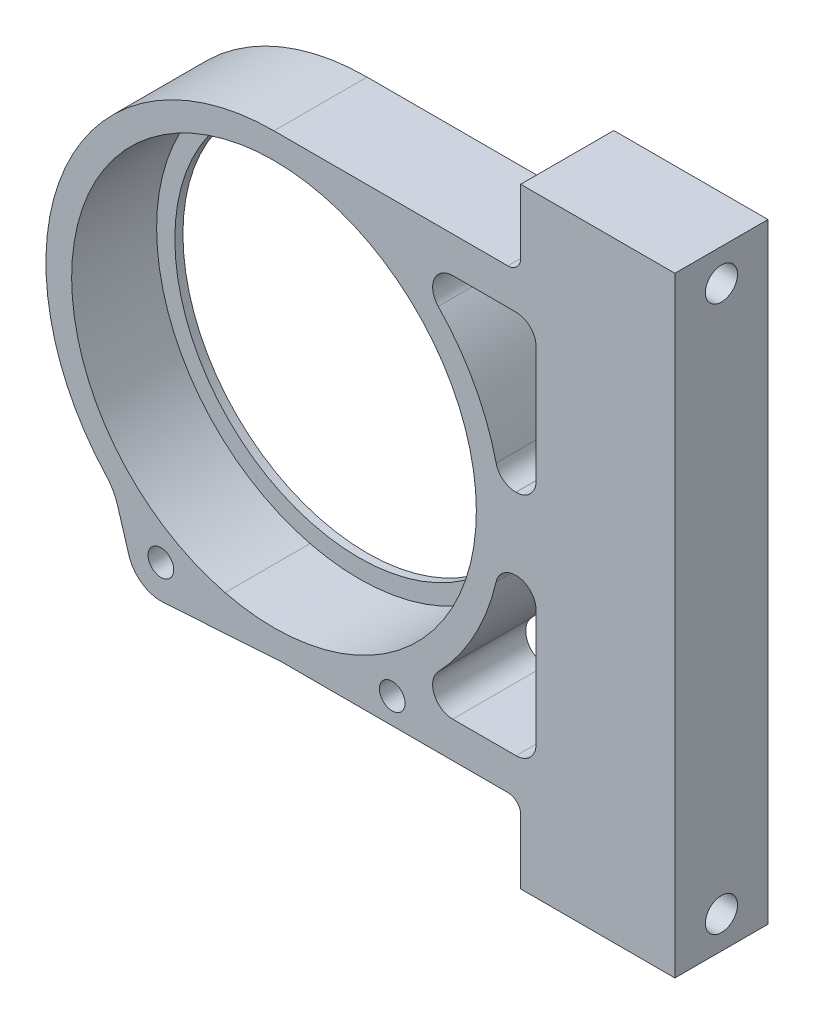
SolidWorks part; units mm, degrees
material "7075-T6 (SN)"
ref_plane "Front Plane" through (0, 0, 0) normal (0, 0, 1) x (1, 0, 0)
ref_plane "Top Plane" through (0, 0, 0) normal (0, 1, 0) x (1, 0, 0)
ref_plane "Right Plane" through (0, 0, 0) normal (1, 0, 0) x (0, 0, -1)
sketch "Sketch1" plane through (0, 0, 0) normal (0, 0, 1) x (1, 0, 0)
  line L0 (73.66, 75.4) -> (73.66, -75.4)
  line L1 (73.66, -1543.0888) -> (73.66, -1565.832) construction
  line L2 (73.66, 75.4) -> (60.96, 75.4)
  line L3 (60.96, 75.4) -> (60.96, 59.525)
  line L4 (57.785, 56.35) -> (0, 56.35)
  line L5 (73.66, -75.4) -> (60.96, -75.4)
  line L6 (60.96, -75.4) -> (60.96, -59.525)
  line L7 (57.785, -56.35) -> (0, -56.35)
  circle A0 centre (0, 0) radius 50
  arc A1 (0, 56.35) -> (0, -56.35) centre (0, 0) ccw
  circle A2 centre (0, 0) radius 56.35 construction
  arc A3 (60.96, -59.525) -> (57.785, -56.35) centre (57.785, -59.525) ccw
  arc A4 (60.96, 59.525) -> (57.785, 56.35) centre (57.785, 59.525) cw
  point P23 (60.96, 56.35)
  dimension "D1" = 50
  dimension "D5" = 3.175
  dimension "D2" = 6.35
  dimension "D3" = 12.7
  dimension "D4" = 19.05
extrude "Boss-Extrude1" add sketch "Sketch1" against normal blind 23
sketch "Sketch2" plane through (60.96, 0, 0) normal (-1, 0, 0) x (0, 0, 1)
  line L0 (-11.5, 75.4) -> (-11.5, -75.4) construction
  line L1 (-23, 75.4) -> (0, 75.4) construction
  line L2 (-23, -75.4) -> (0, -75.4) construction
  line L3 (-23, 67.4625) -> (0, 67.4625) construction
  line L4 (-23, 75.4) -> (-23, 59.525) construction
  line L5 (0, 75.4) -> (0, 59.525) construction
  line L6 (-23, -67.4625) -> (0, -67.4625) construction
  line L7 (-23, -59.525) -> (-23, -75.4) construction
  line L8 (0, -59.525) -> (0, -75.4) construction
  circle A0 centre (-11.5, 67.4625) radius 3.9687
  circle A1 centre (-11.5, -67.4625) radius 3.9687
  circle A2 centre (-11.5, 67.4625) radius 7.1374 construction
  dimension "D1" = 7.9375
  dimension "D2" = 14.2748
extrude "Cut-Extrude1" cut sketch "Sketch2" against normal blind 23
sketch "Sketch3" plane through (0, 0, -23) normal (0, 0, -1) x (-1, 0, 0)
  circle A0 centre (0, 0) radius 50 construction
  circle A1 centre (0, 0) radius 50
  circle A2 centre (0, 0) radius 45.5
  dimension "D1" = 45.5
extrude "Boss-Extrude2" add sketch "Sketch3" against normal blind 2
ref_plane "Plane1" through (0, 0, 0) normal (-0.9703, 0.2419, 0) x (0, 0, 1)
split line "Split Line1"
ref_plane "Plane2" through (73.66, 0, 0) normal (1, 0, 0) x (0, 0, -1)
ref_axis "Axis1" through (0, 0, -21) along (0, 0, 1)
ref_point "Point1"
sketch "Sketch4" plane through (0, 0, 0) normal (0, 0, 1) x (1, 0, 0)
  line L0 (64.77, 8.89) -> (64.77, 47.46)
  line L1 (64.77, -8.89) -> (64.77, 8.89) construction
  line L5 (57.785, 47.46) -> (0, 47.46)
  line L6 (64.77, 47.46) -> (30.3552, 47.46)
  line L7 (30.3552, -47.46) -> (64.77, -47.46)
  line L9 (0, -56.35) -> (57.785, -56.35) construction
  line L10 (64.77, -75.4) -> (64.77, 75.4)
  line L11 (64.77, -47.46) -> (64.77, -8.89)
  line L12 (56.3373, 0) -> (64.77, 0) construction
  line L13 (55.6315, -8.89) -> (64.77, -8.89)
  line L14 (55.6315, 8.89) -> (64.77, 8.89)
  line L15 (56.3373, 8.89) -> (64.77, 8.89) construction
  line L16 (56.3373, -8.89) -> (64.77, -8.89) construction
  arc A2 (30.3552, -47.46) -> (55.6315, -8.89) centre (0, 0) ccw
  arc A4 (55.6315, 8.89) -> (30.3552, 47.46) centre (0, 0) ccw
  arc A5 (55.6315, -8.89) -> (55.6315, 8.89) centre (0, 0) ccw construction
  dimension "D4" = 8.89
  dimension "D2" = 8.89
  dimension "D3" = 8.89
  dimension "D5" = 8.89
  dimension "D6" = 8.89
extrude "Cut-Extrude2" cut sketch "Sketch4" against normal through all
fillet "Fillet1" radius 4.953 8 edges at (64.77, -47.46, -11.5) (30.3552, -47.46, -11.5) (55.6315, -8.89, -11.5) (64.77, -8.89, -11.5) (64.77, 47.46, -11.5) (64.77, 8.89, -11.5) (55.6315, 8.89, -11.5) (30.3552, 47.46, -11.5)
sketch "Sketch5" plane through (73.66, 0, 0) normal (1, 0, 0) x (0, 0, -1)
  line L0 (11.5, 37.3) -> (11.5, -37.3) construction
  line L1 (15.945, 37.3) -> (15.945, -37.3)
  line L2 (7.055, 37.3) -> (7.055, -37.3)
  line L3 (11.5, -75.4) -> (11.5, -37.3) construction
  line L4 (23, -75.4) -> (0, -75.4) construction
  line L5 (11.5, 37.3) -> (11.5, 75.4) construction
  line L6 (23, 75.4) -> (0, 75.4) construction
  arc A0 (15.945, 37.3) -> (7.055, 37.3) centre (11.5, 37.3) ccw
  arc A1 (7.055, -37.3) -> (15.945, -37.3) centre (11.5, -37.3) ccw
  point P2 (11.5, 0)
  dimension "D1" = 8.89
  dimension "D2" = 38.1
extrude "Cut-Extrude3" [suppressed] cut sketch "Sketch5" against normal blind 16.51
sketch "Sketch6" plane through (0, 0, 0) normal (0, 0, 1) x (1, 0, 0)
  line L0 (-27.94, -50) -> (29.21, -50) construction
  line L1 (60.96, -75.4) -> (73.66, -75.4) construction
  line L2 (-76.2, -120.65) -> (-27.94, -50) construction
  line L3 (73.66, -75.4) -> (73.66, 75.4) construction
  line L4 (-22.8035, -35.7983) -> (-78.4053, -108.1429)
  line L5 (-63.5, -120.65) -> (57.4508, -47.4253)
  line L6 (53.34, -32.6977) -> (-16.51, -32.6977)
  line L7 (-22.8035, -35.7983) -> (-78.4053, -108.1429) construction
  line L8 (-63.5, -120.65) -> (57.4508, -47.4253) construction
  line L9 (53.34, -32.6977) -> (-16.51, -32.6977) construction
  circle A0 centre (-76.2, -120.65) radius 12.7 construction
  arc A2 (-63.5, -120.65) -> (-78.4053, -108.1429) centre (-76.2, -120.65) ccw construction
  circle A3 centre (-27.94, -50) radius 3.175
  circle A4 centre (29.21, -50) radius 3.175
  arc A5 (-16.51, -32.6977) -> (-22.8035, -35.7983) centre (-16.51, -40.6352) ccw
  arc A6 (-63.5, -120.65) -> (-78.4053, -108.1429) centre (-76.2, -120.65) ccw
  arc A7 (57.4508, -47.4253) -> (53.34, -32.6977) centre (53.34, -40.6352) ccw
  arc A8 (-16.51, -32.6977) -> (-22.8035, -35.7983) centre (-16.51, -40.6352) ccw construction
  arc A9 (-63.5, -120.65) -> (-78.4053, -108.1429) centre (-76.2, -120.65) ccw construction
  arc A10 (57.4508, -47.4253) -> (53.34, -32.6977) centre (53.34, -40.6352) ccw construction
  dimension "D1" = 25.4
  dimension "D3" = 6.35
  dimension "D4" = 25.4
  dimension "D5" = 57.15
  dimension "D6" = 44.45
  dimension "D2" = 0
extrude "Cut-Extrude4" cut sketch "Sketch6" against normal blind 30.48
sketch "Sketch8" plane through (0, 0, 0) normal (0, 0, 1) x (1, 0, 0)
  line L0 (-39.5552, -40.1336) -> (-35.8403, -52.3938)
  line L1 (-27.4079, -58.2378) -> (3.6323, -56.2328)
  arc A0 (-30.077, -47.6518) -> (-24.8202, -50.5893) centre (-27.94, -50) ccw
  arc A1 (-35.8403, -52.3938) -> (-27.4079, -58.2378) centre (-27.94, -50) ccw
  arc A3 (-39.5552, -40.1336) -> (-30.077, -47.6518) centre (0, 0) ccw
  arc A5 (-24.8202, -50.5893) -> (3.6323, -56.2328) centre (0, 0) ccw
  circle A6 centre (-27.94, -50) radius 8.255 construction
  circle A8 centre (-27.94, -50) radius 3.175 construction
  arc A9 (0, 56.35) -> (-30.077, -47.6518) centre (0, 0) ccw construction
  arc A10 (-24.8202, -50.5893) -> (0, -56.35) centre (0, 0) ccw construction
  dimension "D2" = 6.35
  dimension "D3" = 15.24
  dimension "D1" = 5.08
extrude "Boss-Extrude4" add sketch "Sketch8" against normal up to surface (23 mm away) up to face at (34.5652, -7.2054, -23)
fillet "Fillet2" radius 12.7 1 edges at (-39.5552, -40.1336, -11.5)
sketch "Sketch9" plane through (73.66, 0, 0) normal (1, 0, 0) x (0, 0, -1)
  line L1 (0, 75.4) -> (23, 75.4)
  line L2 (0, 75.4) -> (0, -75.4)
  line L3 (0, -75.4) -> (23, -75.4)
  line L4 (23, 75.4) -> (23, -75.4)
  circle A0 centre (11.5, 67.4625) radius 3.9687
  circle A1 centre (11.5, -67.4625) radius 3.9687
  dimension "D1" = 7.9375
  dimension "D2" = 7.9375
extrude "Boss-Extrude5" add sketch "Sketch9" along normal blind 25.4
